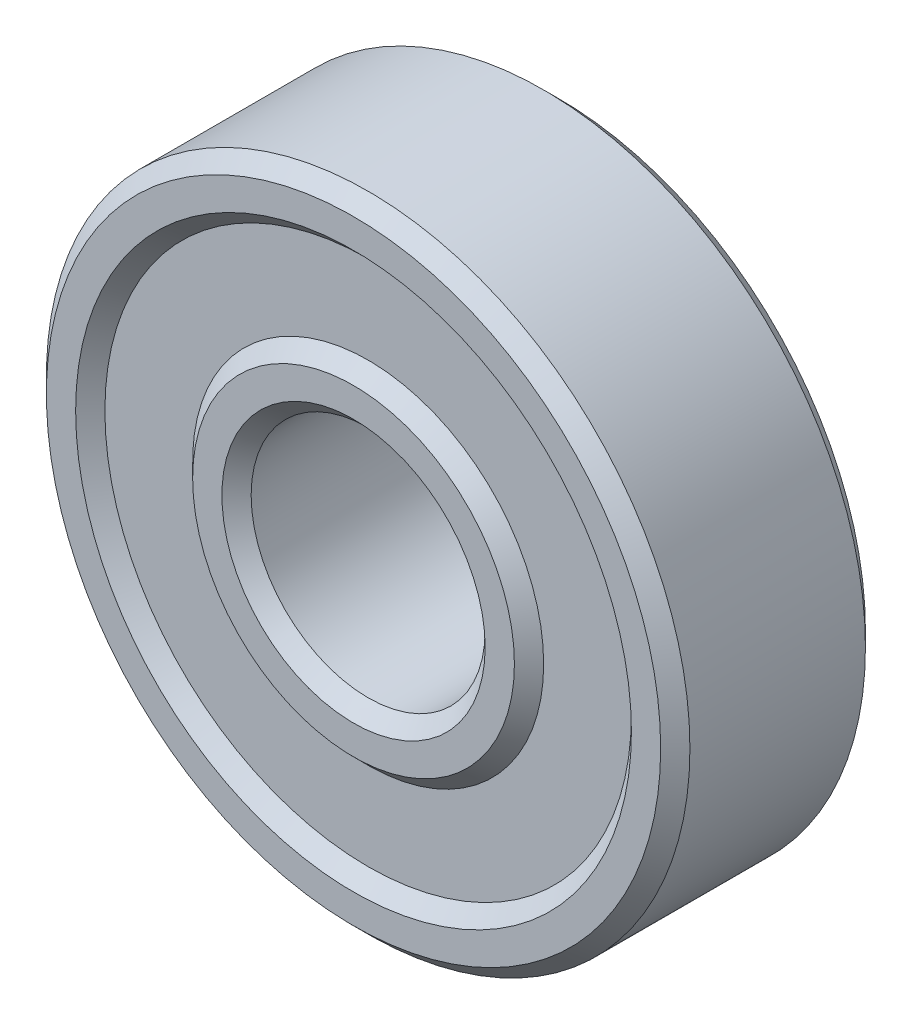
SolidWorks part; units mm, degrees
ref_plane "Front Plane" through (0, 0, 0) normal (0, 0, 1) x (1, 0, 0)
ref_plane "Top Plane" through (0, 0, 0) normal (0, 1, 0) x (1, 0, 0)
ref_plane "Right Plane" through (0, 0, 0) normal (1, 0, 0) x (0, 0, -1)
sketch "Sketch1" plane through (0, 0, 0) normal (0, 0, 1) x (1, 0, 0)
  circle A0 centre (0, 0) radius 11
  circle A1 centre (0, 0) radius 4
  circle A2 centre (0, 0) radius 9
  circle A3 centre (0, 0) radius 6
  dimension "D1" = 8
  dimension "D2" = 22
  dimension "D3" = 2
  dimension "D4" = 2
extrude "Boss-Extrude1" add sketch "Sketch1" along normal mid plane 7 contours A0 | A1
extrude "Cut-Extrude1" cut sketch "Sketch1<3>" along normal blind 0.5 from surface contours A2 A3 region at (-8.7454, 0, 0) starting at face at (11, 0, -3.5)
sketch "Sketch1<3>" plane through (0, 0, 0) normal (0, 0, 1) x (1, 0, 0) same geometry as "Sketch1"
extrude "Cut-Extrude2" cut sketch "Sketch1<4>" against normal blind 0.5 from surface contours A2 A3 region at (-8.7454, 0, 0) starting at face at (11, 0, 3.5)
sketch "Sketch1<4>" plane through (0, 0, 0) normal (0, 0, 1) x (1, 0, 0) same geometry as "Sketch1"
chamfer "Chamfer1" distance 0.5 angle 45 8 edges at (9, 0, -3.5) (4, 0, -3.5) (6, 0, -3.5) (6, 0, 3.5) (4, 0, 3.5) (9, 0, 3.5) (11, 0, -3.5) (11, 0, 3.5)
